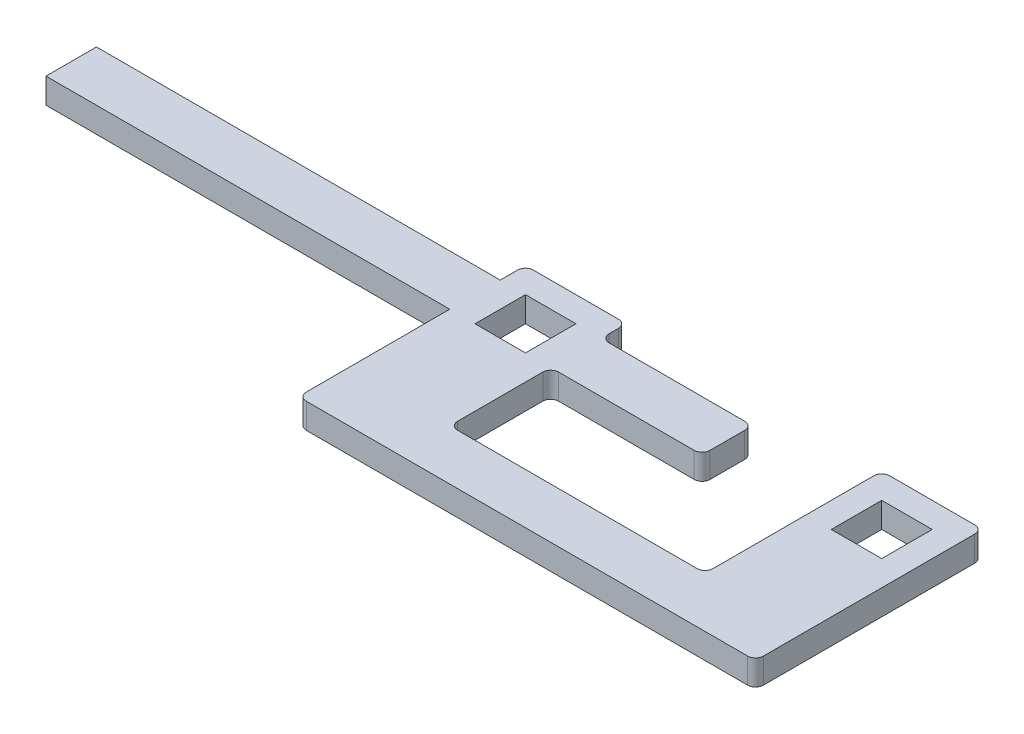
SolidWorks part; units mm, degrees
material "Beech"
ref_plane "Front Plane" through (0, 0, 0) normal (0, 0, 1) x (1, 0, 0)
ref_plane "Top Plane" through (0, 0, 0) normal (0, 1, 0) x (1, 0, 0)
ref_plane "Right Plane" through (0, 0, 0) normal (1, 0, 0) x (0, 0, -1)
sketch "Sketch1" plane through (0, 0, 0) normal (0, 1, 0) x (1, 0, 0)
  line L0 (0, 0) -> (0, 19.05)
  line L1 (0, 0) -> (19.05, 0)
  line L2 (0, 28.575) -> (12.7, 28.575)
  line L3 (12.7, 6.35) -> (12.7, 19.05)
  line L4 (44.8249, 28.575) -> (44.8249, 6.35)
  line L5 (44.8249, 28.575) -> (57.5249, 28.575)
  line L6 (42.65, 0) -> (57.5249, 0)
  line L7 (57.5249, 28.575) -> (57.5249, 0)
  line L8 (12.7, 6.35) -> (44.8249, 6.35)
  line L10 (12.7, 19.05) -> (31.75, 19.05)
  line L11 (19.05, 0) -> (42.65, 0)
  line L12 (3.175, 25.4) -> (3.175, 19.05)
  line L13 (3.175, 25.4) -> (9.525, 25.4)
  line L14 (3.175, 19.05) -> (9.525, 19.05)
  line L15 (9.525, 25.4) -> (9.525, 19.05)
  line L16 (47.9999, 25.4) -> (47.9999, 19.05)
  line L17 (47.9999, 25.4) -> (54.3499, 25.4)
  line L18 (47.9999, 19.05) -> (54.3499, 19.05)
  line L19 (54.3499, 25.4) -> (54.3499, 19.05)
  line L20 (0, 25.4) -> (-50.8, 25.4)
  line L21 (12.7, 25.4) -> (31.75, 25.4)
  line L22 (-50.8, 25.4) -> (-50.8, 19.05)
  line L23 (0, 19.05) -> (-50.8, 19.05)
  line L24 (0, 25.4) -> (0, 28.575)
  line L25 (31.75, 19.05) -> (31.75, 25.4)
  line L26 (12.7, 25.4) -> (12.7, 28.575)
  dimension "D1" = 6.35
  dimension "D2" = 6.35
  dimension "D3" = 6.35
  dimension "D4" = 6.35
  dimension "D5" = 44.8249
  dimension "D6" = 3.175
  dimension "D7" = 19.05
  dimension "D8" = 3.175
  dimension "D9" = 3.175
  dimension "D10" = 3.175
  dimension "D11" = 3.175
  dimension "D12" = 3.175
  dimension "D13" = 19.05
  dimension "D14" = 50.8
  dimension "D15" = 6.35
  dimension "D16" = 6.35
  dimension "D17" = 19.05
extrude "Elastic_Extrude" add sketch "Sketch1" along normal blind 3.175
fillet "Elastic_CornerFillet" radius 1 12 edges at (12.7, 1.5875, -6.35) (44.8249, 1.5875, -6.35) (44.8249, 1.5875, -28.575) (57.5249, 1.5875, -28.575) (57.5249, 1.5875, 0) (0, 1.5875, 0) (0, 1.5875, -28.575) (12.7, 1.5875, -19.05) (31.75, 1.5875, -19.05) (31.75, 1.5875, -25.4) (12.7, 1.5875, -25.4) (12.7, 1.5875, -28.575)
equation "\"CageLeftBottomEdge\"=22.11mm"
equation "\"CageLeftTopEdge\"=22.11mm"
equation "\"CageRightBottomEdge\"=21.63mm"
equation "\"CageRightTopEdge\"=21.63mm"
equation "\"CageHeight\"=86.04mm"
equation "\"CageLength\"=73.76mm"
equation "\"CageTopScrewClearance\"=10mm"
equation "\"CageBottomScrewClearance\"=25mm"
equation "\"CageLeftTopDepth\"= 11.65mm"
equation "\"CageLeftBottomDepth\"=11.11mm"
equation "\"CageLeftTopHeight\"=8.56175mm"
equation "\"CageLeftBottomHeight\"=16mm"
equation "\"CageRightTopDepth\"= 11.05mm"
equation "\"CageRightBottomDepth\"=10.58mm"
equation "\"CageRightTopHeight\"=9.6mm"
equation "\"CageRightBottomHeight\"=15.49mm"
equation "\"CageLeftTopChannelDepth\"=2.41908mm"
equation "\"CageLeftBottomChannelDepth\"=2.588mm"
equation "\"CageLeftChannelHeight\"=11.7mm"
equation "\"CageRightTopChannelDepth\"=2.32mm"
equation "\"CageRightBottomChannelDepth\"=2.318mm"
equation "\"CageRightChannelHeight\"=10mm"
equation "\"CageChanRelHeight\"=23.99mm"
equation "\"CageChanRelDepth\"=5.492mm"
equation "\"CageChamberRadius\"=16.261mm"
equation "\"CageScrewDiameter\"=4.8mm"
equation "\"CageSetScrewDiameter\"=3.5mm"
equation "\"CageAxleRadius\"=6.639mm"
equation "\"CageAxleKeyHeight\"=1.619mm"
equation "\"CageAxleKeyWidth\"=2.662mm"
equation "\"CageHoseWindowWidth\"=16.29mm"
equation "\"CageHoseWindowHeight\"=26.5mm"
equation "\"CageHoseWindow-Edge\"=8.89mm"
equation "\"CageScrew-VerticalEdge\"=5.0mm"
equation "\"CageScrew-HorizontalEdge\"=7.5mm"
equation "\"CageScrew-HoseCornerScrewEdge\"=4.45mm"
equation "\"CageAxle-BottomEdge\"=56.05mm"
equation "\"CageAxle-FrontEdge\"=46.03mm"
equation "\"CageBackSetScrew-Axle\"=40mm"
equation "\"CageFrontSetScrew-Axle\"=22mm"
equation "\"CageVelocityWindow-BackEdge\"=34.8mm"
equation "\"CageVelocityWindow-BottomEdge\"=27.55mm"
equation "\"CageVelocityWindowHeight\"=22.29mm"
equation "\"CageVelocityWindowWidth\"=12.61mm"
equation "\"TriggerSlot-BottomEdge\"=6.35mm"
equation "\"TriggerSlot-FrontEdge\"=15mm"
equation "\"TriggerSlotSize\"=6.7mm"
equation "\"TriggerRackOffset\"=.236224in"
equation "\"TriggerSlotSizeInt\"=.25in"
equation "\"MotorMountLegLength\"=.25in"
equation "\"GearOffset\"=.264907in"
equation "\"TriggerSlotSpacing\"=.25in"
equation "\"TriggerMiniSlotWidth\"=3.5mm"
equation "\"TriggerRackWidth\"=6.5mm"
equation "\"TGMGearFaceDiameter\"=24.40mm"
equation "\"TGMCylinderLength\"=15.00mm"
equation "\"TGMScrewHole-Center\"=8.70mm"
equation "\"TGMScrewHoleDiameter\"=5.04mm"
equation "\"TGMCenterHoleDiameter\"=9.50mm"
equation "\"TGMShaftCollarSideLength\"=19.00mm"
equation "\"TGMShaftCollarDockingDepth\"=7.00mm"
equation "\"whitemotordepth\"=11.27mm"
equation "\"whitemotorbackdepth\"=3.845mm"
equation "\"whitemotoraxledepth\" = 3.5mm"
equation "\"whitemotoraxleoffset\"=11.4mm"
equation "\"whitemotorwidth\"=12.07mm"
equation "\"whitemotorheight\"=16.68mm"
equation "\"whitemotorcylinderlength\" =13.04mm"
equation "\"whitemotorcylinderradius\"=3.845mm"
equation "\"whitemotorcylinderoffset\"=2.35mm"
equation "\"whitemotorcutoutlength\"=1.88mm"
equation "\"whitemotorouterrad\"=5mm"
equation "\"D4@Sketch1\"=\"elasticrackpegsize\""
equation "\"elasticrackpegspacing\"=1.76476"
equation "\"D5@Sketch1\"=\"elasticrackpegspacing\""
equation "\"D6@Sketch1\"=\"elasticrackpegbuffer\""
equation "\"elasticrackpegsize\"=.25in"
equation "\"D1@Sketch1\"=\"elasticrackpegsize\""
equation "\"D2@Sketch1\"=\"elasticrackpegsize\""
equation "\"D3@Sketch1\"=\"elasticrackpegsize\""
equation "\"elasticracklength\"=2in"
equation "\"D14@Sketch1\"=\"elasticracklength\""
equation "\"elasticrackpegbuffer\"=.125in"
equation "\"D11@Sketch1\"=\"elasticrackpegbuffer\""
equation "\"D12@Sketch1\"=\"elasticrackpegbuffer\""
equation "\"D10@Sketch1\"=\"elasticrackpegbuffer\""
equation "\"D9@Sketch1\"=\"elasticrackpegbuffer\""
equation "\"D8@Sketch1\"=\"elasticrackpegbuffer\""
equation "\"elasticbaybuffer\"=.25in"
equation "\"D15@Sketch1\"=\"elasticbaybuffer\""
equation "\"D16@Sketch1\"=\"elasticbaybuffer\""
equation "\"whitemotorinnerrad\"=2.95mm"
equation "\"elasticbaydepth\"=.75in"
equation "\"D7@Sketch1\"=\"elasticbaydepth\""
equation "\"D13@Sketch1\"=\"elasticbaydepth\""
equation "\"D17@Sketch1\"=\"elasticbaydepth\""
equation "\"elasticdepth\"=.125in"
equation "\"D1@Elastic_Extrude\"=\"elasticdepth\""
